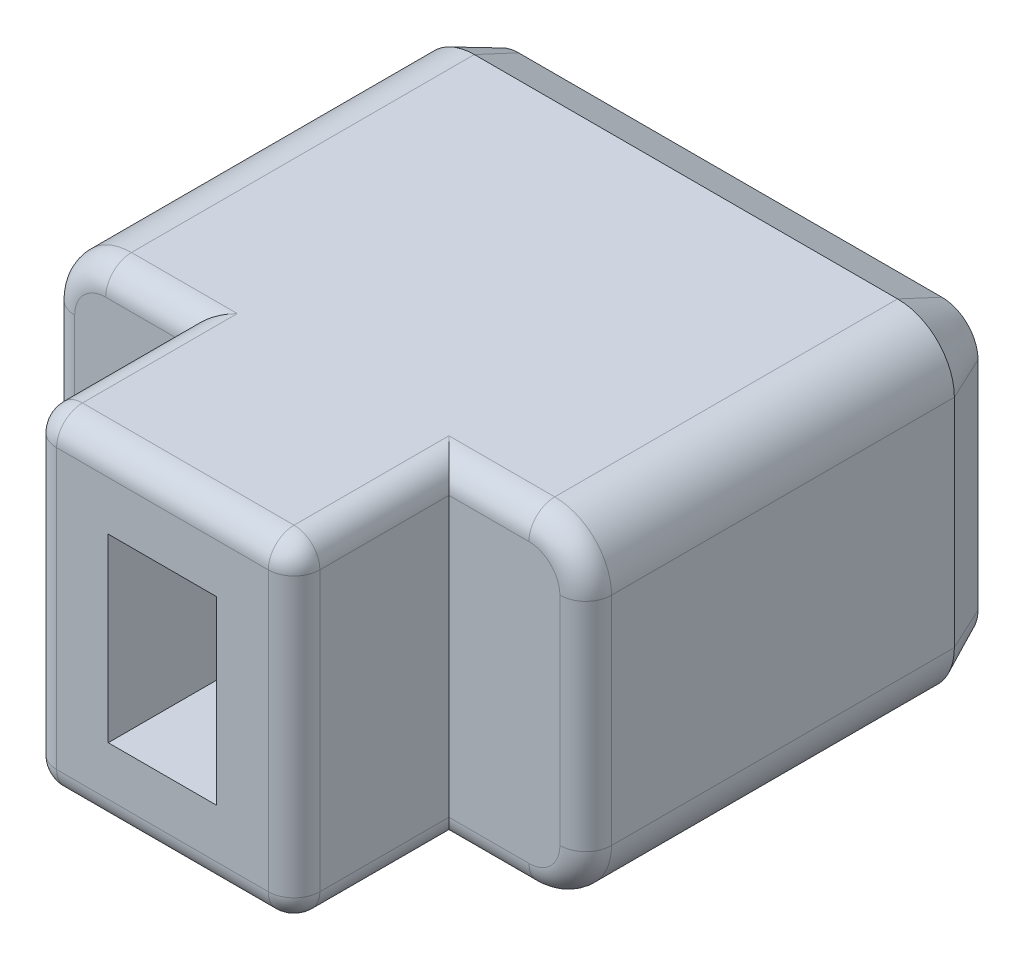
SolidWorks part; units mm, degrees
ref_plane "Plan de face" through (0, 0, 0) normal (0, 0, 1) x (1, 0, 0)
ref_plane "Plan de dessus" through (0, 0, 0) normal (0, 1, 0) x (1, 0, 0)
ref_plane "Plan de droite" through (0, 0, 0) normal (1, 0, 0) x (0, 0, -1)
sketch "Esquisse2" plane through (0, 0, 0) normal (0, 0, 1) x (1, 0, 0)
  line L1 (1.1, 0) -> (9.3, 0)
  line L2 (0, 1.1) -> (0, 5.3)
  line L3 (1.1, 6.4) -> (9.3, 6.4)
  line L4 (10.4, 1.1) -> (10.4, 5.3)
  arc A0 (9.3, 6.4) -> (10.4, 5.3) centre (9.3, 5.3) cw
  arc A1 (9.3, 0) -> (10.4, 1.1) centre (9.3, 1.1) ccw
  arc A2 (1.1, 0) -> (0, 1.1) centre (1.1, 1.1) cw
  arc A3 (0, 5.3) -> (1.1, 6.4) centre (1.1, 5.3) cw
  point P7 (10.4, 6.4)
  point P12 (0, 0)
  point P15 (0, 6.4)
  dimension "D3" = 1.1
  dimension "D1" = 10.4
  dimension "D2" = 6.4
extrude "Boss.-Extru.1" add sketch "Esquisse2" along normal blind 11
sketch "Esquisse3" plane through (0, 0, 11) normal (0, 0, 1) x (1, 0, 0)
  line L0 (0, 5.3) -> (0, 1.1) construction
  line L1 (4.15, 4.95) -> (6.25, 4.95)
  line L2 (4.15, 4.95) -> (4.15, 1.45)
  line L3 (4.15, 1.45) -> (6.25, 1.45)
  line L4 (6.25, 4.95) -> (6.25, 1.45)
  line L5 (10.4, 1.1) -> (10.4, 5.3) construction
  line L6 (9.3, 6.4) -> (1.1, 6.4) construction
  line L7 (1.1, 0) -> (9.3, 0) construction
  dimension "D1" = 2.1
  dimension "D2" = 3.5
  dimension "D3" = 4.15
  dimension "D4" = 4.15
  dimension "D5" = 1.45
  dimension "D6" = 1.45
extrude "Enlèv. mat.-Extru.1" cut sketch "Esquisse3" against normal blind 3
sketch "Esquisse4" plane through (0, 0, 11) normal (0, 0, 1) x (1, 0, 0)
  line L0 (2.65, 6.4) -> (2.65, 0)
  line L1 (9.3, 6.4) -> (1.1, 6.4) construction
  line L2 (1.1, 0) -> (9.3, 0) construction
  line L3 (2.65, 0) -> (7.75, 0)
  line L4 (7.75, 0) -> (7.75, 6.4)
  line L5 (7.75, 6.4) -> (2.65, 6.4)
  line L6 (4.15, 4.95) -> (4.15, 1.45) construction
  line L7 (6.25, 1.45) -> (6.25, 4.95) construction
  dimension "D1" = 1.5
  dimension "D2" = 1.5
extrude "Enlèv. mat.-Extru.2" cut sketch "Esquisse4" against normal blind 3 flip side to cut
fillet "Congé1" radius 0.5 18 edges at (8.525, 0, 8) (10.0778, 0.3222, 8) (10.4, 3.2, 8) (10.0778, 6.0778, 8) (1.875, 6.4, 8) (0.3222, 6.0778, 8) (1.875, 0, 8) (0.3222, 0.3222, 8) (7.75, 6.4, 9.5) (2.65, 6.4, 9.5) (7.75, 0, 9.5) (2.65, 0, 9.5) (2.65, 3.2, 11) (5.2, 6.4, 11) (7.75, 3.2, 11) (5.2, 0, 11) (8.525, 6.4, 8) (0, 3.2, 8)
chamfer "Chanfrein1" distance 0.4 angle 65 8 edges at (5.2, 0, 0) (10.0778, 0.3222, 0) (0.3222, 0.3222, 0) (10.4, 3.2, 0) (0, 3.2, 0) (10.0778, 6.0778, 0) (0.3222, 6.0778, 0) (5.2, 6.4, 0) first distance on face at (5.2, 3.2, 0)
sketch "Esquisse5" plane through (0, 0, 0) normal (0, 0, -1) x (-1, 0, 0)
  line L0 (-0.4, 5.3) -> (-10, 5.3) construction
  arc A0 (-9.3, 6) -> (-10, 5.3) centre (-9.3, 5.3) ccw construction
  text T0 "1" font "Century Gothic" height 4
extrude "Enlèv. mat.-Extru.3" cut sketch "Esquisse5" against normal blind 0.3
extrude "Boss.-Extru.2" add sketch "Esquisse5<2>" along normal blind 0.3 separate body
sketch "Esquisse5<2>" plane through (0, 0, 0) normal (0, 0, -1) x (-1, 0, 0) same geometry as "Esquisse5"
